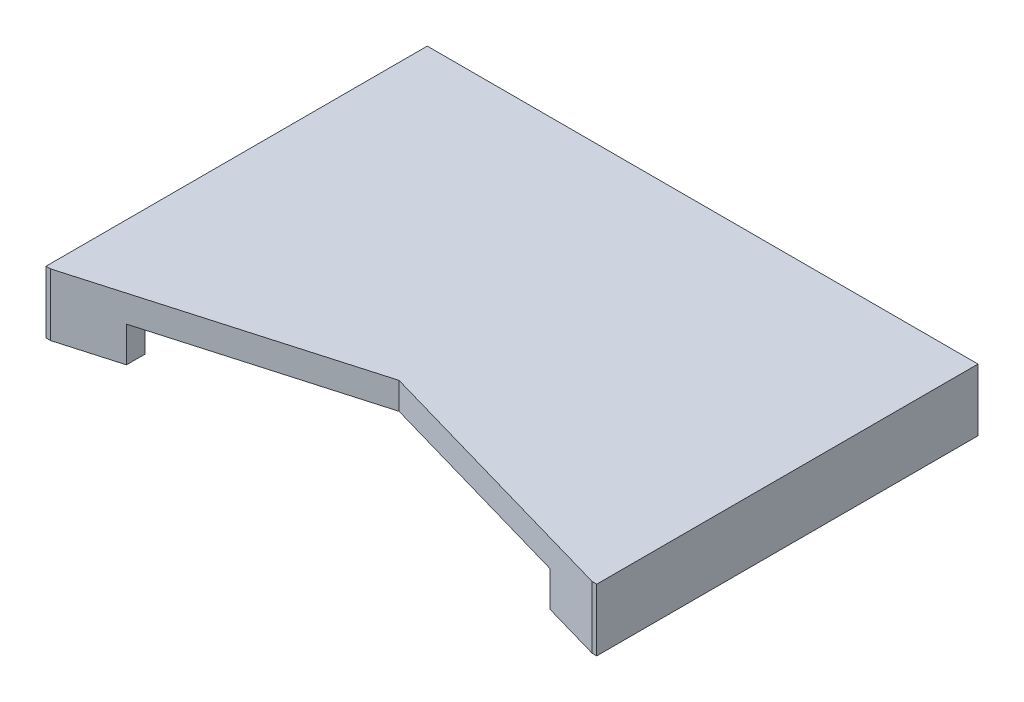
SolidWorks part; units mm, degrees
ref_plane "Front Plane" through (0, 0, 0) normal (0, 0, 1) x (1, 0, 0)
ref_plane "Top Plane" through (0, 0, 0) normal (0, 1, 0) x (1, 0, 0)
ref_plane "Right Plane" through (0, 0, 0) normal (1, 0, 0) x (0, 0, -1)
sketch "Sketch1" plane through (0, 0, 0) normal (0, 1, 0) x (1, 0, 0)
  line L1 (0, 0) -> (78, 0)
  line L2 (0, 0) -> (0, 54)
  line L3 (0, 54) -> (78, 54)
  line L4 (78, 0) -> (78, 54)
  dimension "D1" = 54
  dimension "D2" = 78
extrude "Boss-Extrude1" add sketch "Sketch1" along normal blind 8.8
sketch "Sketch2" plane through (0, 0, 0) normal (0, -1, 0) x (1, 0, 0)
  line L0 (78, -54) -> (0, -54) construction
  line L1 (6, -54) -> (72, -54)
  line L2 (6, -54) -> (6, -5)
  line L3 (6, -5) -> (72, -5)
  line L4 (72, -54) -> (72, -5)
  line L5 (0, -54) -> (0, 0) construction
  line L6 (78, 0) -> (78, -54) construction
  line L7 (0, 0) -> (78, 0) construction
  dimension "D1" = 6
  dimension "D2" = 6
  dimension "D3" = 5
extrude "Cut-Extrude1" cut sketch "Sketch2" against normal blind 5
sketch "Sketch3" plane through (0, 0, 0) normal (0, -1, 0) x (1, 0, 0)
  line L0 (72, -5) -> (6, -5) construction
  line L1 (9, -5) -> (69, -5)
  line L2 (9, -5) -> (9, 0)
  line L3 (9, 0) -> (69, 0)
  line L4 (69, -5) -> (69, 0)
  line L5 (0, 0) -> (78, 0) construction
  line L6 (0, -54) -> (0, 0) construction
  line L7 (78, 0) -> (78, -54) construction
  dimension "D1" = 9
  dimension "D2" = 9
extrude "Cut-Extrude2" cut sketch "Sketch3" against normal up to surface (5 mm away) up to face at (39, 5, -29.5)
sketch "Sketch4" plane through (0, 8.8, 0) normal (0, 1, 0) x (1, 0, 0)
  line L0 (0, 0) -> (78, 0) construction
  line L1 (0.6384, 0) -> (39, 11)
  line L2 (39, 11) -> (77.3616, 0)
  line L3 (39, 11) -> (39, 54) construction
  line L4 (77.3616, 0) -> (0.6384, 0)
  line L5 (78, 54) -> (0, 54) construction
  dimension "D1" = 148
  dimension "D3" = 11
extrude "Cut-Extrude3" cut sketch "Sketch4" against normal up to next
